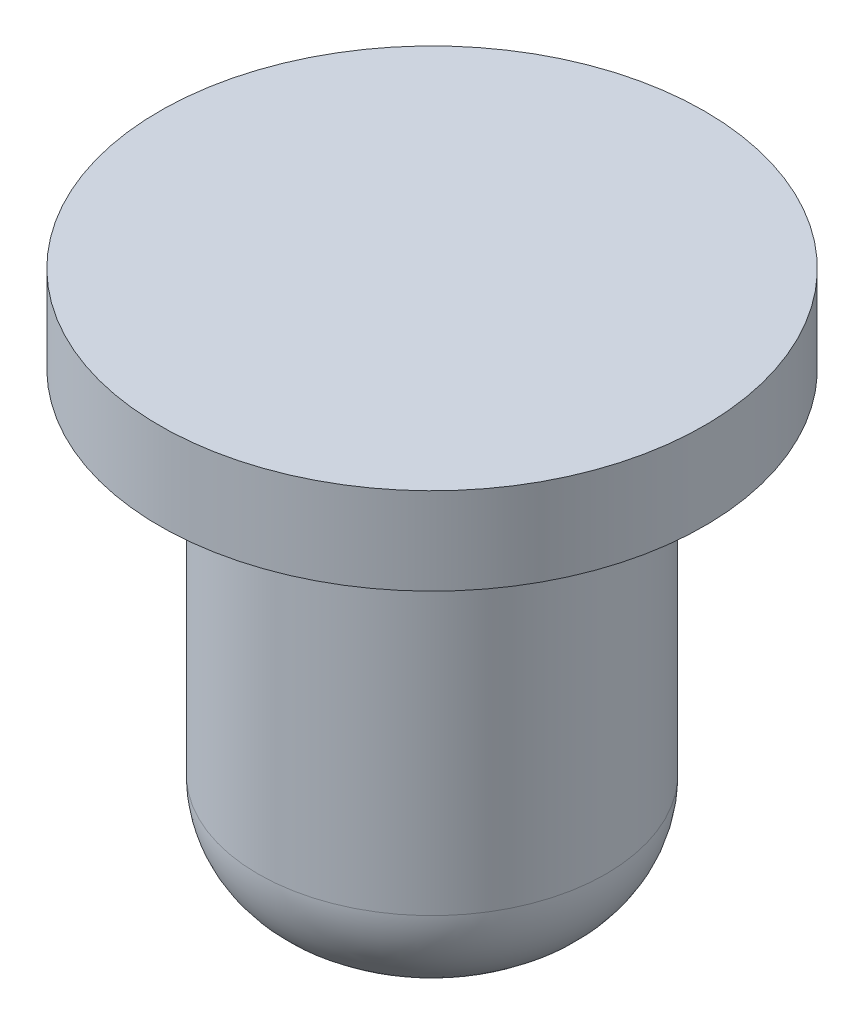
SolidWorks part; units mm, degrees
ref_plane "Front Plane" through (0, 0, 0) normal (0, 0, 1) x (1, 0, 0)
ref_plane "Top Plane" through (0, 0, 0) normal (0, 1, 0) x (1, 0, 0)
ref_plane "Right Plane" through (0, 0, 0) normal (1, 0, 0) x (0, 0, -1)
sketch "Sketch1" plane through (0, 0, 0) normal (0, 0, 1) x (1, 0, 0)
  line L0 (0, 18.6267) -> (19.8967, 18.6267)
  line L1 (19.8967, 18.6267) -> (19.8967, 12.2767)
  line L2 (19.8967, 12.2767) -> (12.7, 12.2767)
  line L3 (12.7, 12.2767) -> (12.7, -13.335)
  line L4 (5.08, -20.955) -> (0, -20.955)
  line L5 (0, -20.955) -> (0, 18.6267)
  arc A0 (12.7, -13.335) -> (5.08, -20.955) centre (5.08, -13.335) cw
  point P9 (12.7, -20.955)
  dimension "D2" = 7.62
  dimension "D1" = 12.7
revolve "Revolve1" add sketch "Sketch1" angle 360 about L5
